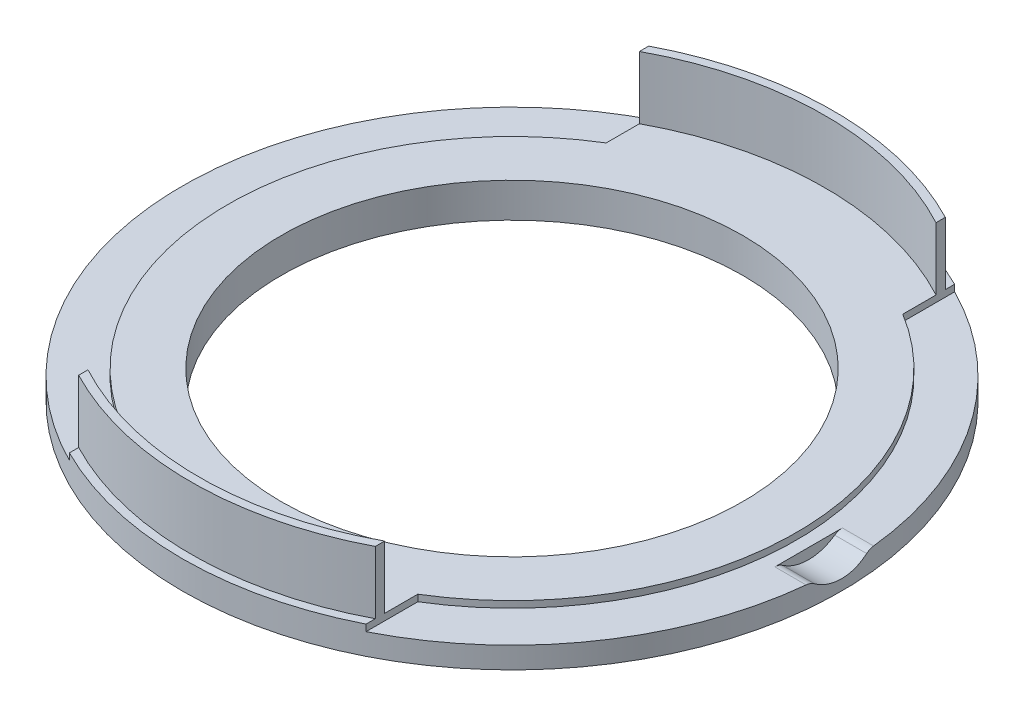
SolidWorks part; units mm, degrees
ref_plane "Front Plane" through (0, 0, 0) normal (0, 0, 1) x (1, 0, 0)
ref_plane "Top Plane" through (0, 0, 0) normal (0, 1, 0) x (1, 0, 0)
ref_plane "Right Plane" through (0, 0, 0) normal (1, 0, 0) x (0, 0, -1)
sketch "Sketch1" plane through (0, 0, 0) normal (0, 1, 0) x (1, 0, 0)
  circle A0 centre (0, 0) radius 20
  circle A1 centre (0, 0) radius 14
  dimension "D1" = 40
  dimension "D2" = 28
extrude "Boss-Extrude1" add sketch "Sketch1" along normal blind 1.3
sketch "Sketch2" plane through (0, 0, 0) normal (0, -1, 0) x (1, 0, 0)
  circle A0 centre (0, 0) radius 14
  circle A1 centre (0, 0) radius 17.25
  dimension "D1" = 34.5
extrude "Boss-Extrude2" add sketch "Sketch2" along normal blind 0.4 and the other way blind 1.7
sketch "Sketch3" plane through (0, 1.3, 0) normal (0, 1, 0) x (1, 0, 0)
  line L0 (6.7354, 12.2733) -> (9, 12.2733)
  line L1 (-9, -11.4979) -> (-7.9874, -11.4979)
  line L2 (-9, -11.4979) -> (-9, -17.8606)
  line L4 (9, -11.4979) -> (9, -17.8606)
  line L5 (-9, -11.4979) -> (3.7483, -19.6456) construction
  line L6 (-3.7483, -19.6456) -> (9, -11.4979) construction
  line L7 (7.9874, -11.4979) -> (9, -11.4979)
  line L8 (-9, 17.8606) -> (-9, 12.2733)
  line L9 (-9, 12.2733) -> (-6.7354, 12.2733)
  line L10 (9, 17.8606) -> (9, 12.2733)
  line L11 (-4.176, 19.5592) -> (9, 12.2733) construction
  line L12 (-9, 12.2733) -> (4.176, 19.5592) construction
  circle A0 centre (0, 0) radius 17.25 construction
  circle A1 centre (0, 0) radius 17.25 construction
  arc A2 (-9, -17.8606) -> (9, -17.8606) centre (0, 0) ccw
  arc A3 (6.7354, 12.2733) -> (-6.7354, 12.2733) centre (0, 0) ccw
  arc A4 (9, 17.8606) -> (-9, 17.8606) centre (0, 0) ccw
  arc A5 (-7.9874, -11.4979) -> (7.9874, -11.4979) centre (0, 0) ccw
  point P0 (0, -17.25)
  point P9 (0, 17.25)
  dimension "D1" = 18
  dimension "D2" = 18
extrude "Boss-Extrude3" add sketch "Sketch3" along normal blind 0.4
ref_plane "Plane1" through (20, 0, 0) normal (1, 0, 0) x (0, 0, -1)
sketch "Sketch4" plane through (20, 0, 0) normal (1, 0, 0) x (0, 0, -1)
  line L0 (-17.25, 0) -> (17.25, 0) construction
  circle A0 centre (0, 3.4) radius 2.75
  dimension "D1" = 5.5
  dimension "D2" = 3.4
extrude "Cut-Extrude1" cut sketch "Sketch4" against normal blind 2
fillet "Fillet1" radius 0.8 2 edges at (18.9605, 1.3, 1.7755) (18.9605, 1.3, -1.7755)
sketch "Sketch5" plane through (0, 1.7, 0) normal (0, 1, 0) x (1, 0, 0)
  line L0 (9, -17.2988) -> (9, -16.7332)
  line L1 (9, -17.8606) -> (9, -14.7161) construction
  line L2 (-9, -17.2988) -> (-9, -16.7332)
  line L3 (-9, -14.7161) -> (-9, -17.8606) construction
  line L4 (9, 16.7332) -> (9, 17.2988)
  line L5 (9, 14.7161) -> (9, 17.8606) construction
  line L6 (-9, 16.7332) -> (-9, 17.2988)
  line L7 (-9, 17.8606) -> (-9, 14.7161) construction
  arc A0 (9, 16.7332) -> (-9, 16.7332) centre (0, 0) ccw
  arc A1 (9, 17.2988) -> (-9, 17.2988) centre (0, 0) ccw
  arc A2 (-9, -16.7332) -> (9, -16.7332) centre (0, 0) ccw
  arc A3 (-9, -17.2988) -> (9, -17.2988) centre (0, 0) ccw
  dimension "D1" = 38
  dimension "D2" = 0.5
extrude "Boss-Extrude4" add sketch "Sketch5" along normal blind 3.8
